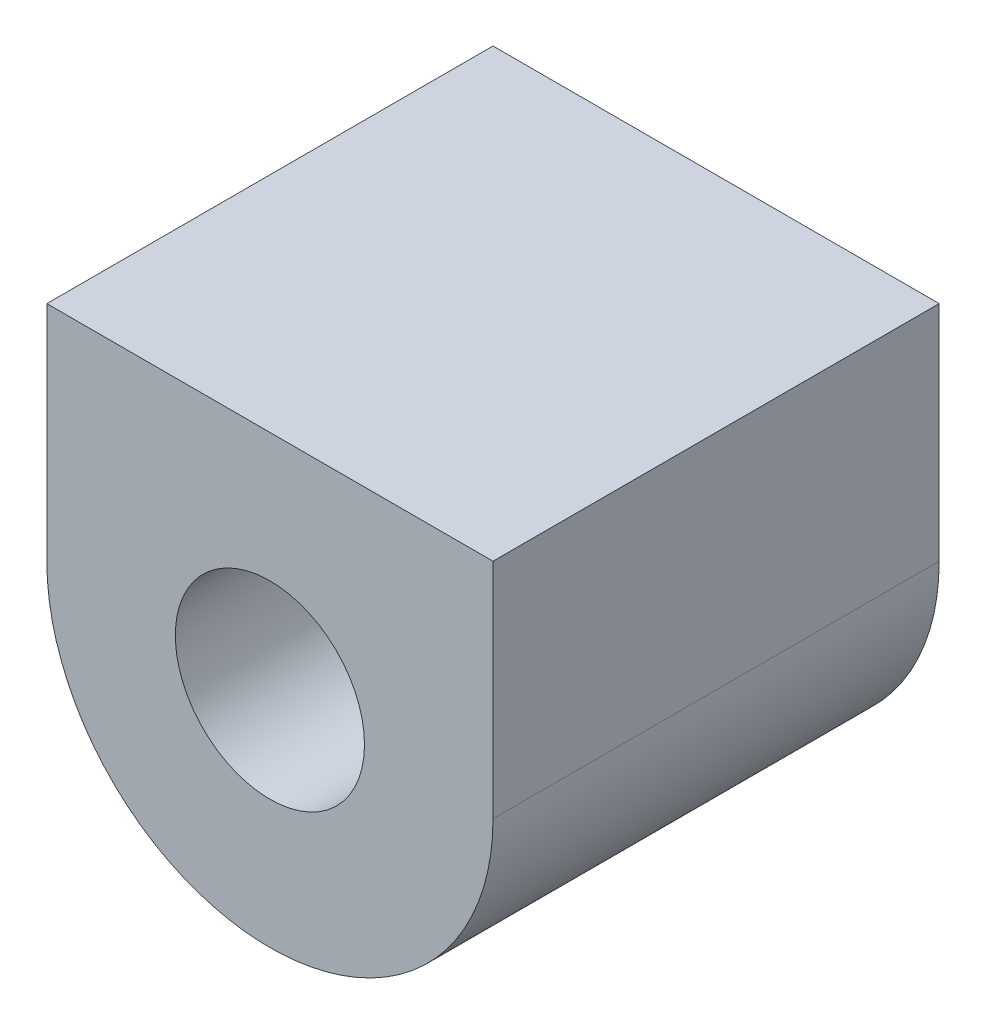
SolidWorks part; units mm, degrees
ref_plane "Front Plane" through (0, 0, 0) normal (0, 0, 1) x (1, 0, 0)
ref_plane "Top Plane" through (0, 0, 0) normal (0, 1, 0) x (1, 0, 0)
ref_plane "Right Plane" through (0, 0, 0) normal (1, 0, 0) x (0, 0, -1)
sketch "Sketch1" plane through (0, 0, 0) normal (0, 1, 0) x (1, 0, 0)
  line L1 (-12.5, -12.5) -> (12.5, -12.5)
  line L2 (-12.5, -12.5) -> (-12.5, 12.5)
  line L3 (-12.5, 12.5) -> (12.5, 12.5)
  line L4 (12.5, -12.5) -> (12.5, 12.5)
  line L5 (-12.5, -12.5) -> (12.5, 12.5) construction
  line L6 (-12.5, 12.5) -> (12.5, -12.5) construction
  point P0 (0, 0)
  dimension "D1" = 25
  dimension "D2" = 25
extrude "Boss-Extrude1" add sketch "Sketch1" along normal blind 25
sketch "Sketch2" plane through (0, 0, 12.5) normal (0, 0, 1) x (1, 0, 0)
  line L0 (-12.5, 0) -> (12.5, 0) construction
  circle A0 centre (0, 12.5) radius 5.3
  point P2 (0, 0)
  dimension "D1" = 10.6
  dimension "D2" = 12.5
extrude "Cut-Extrude1" cut sketch "Sketch2" against normal through all
fillet "Fillet1" 2 edges at (-12.5, 0, 0) (12.5, 0, 0) type full round first side face at (-12.5, 12.5, 0) second side face at (12.5, 12.5, 0) middle face at (0, 0, 0)
